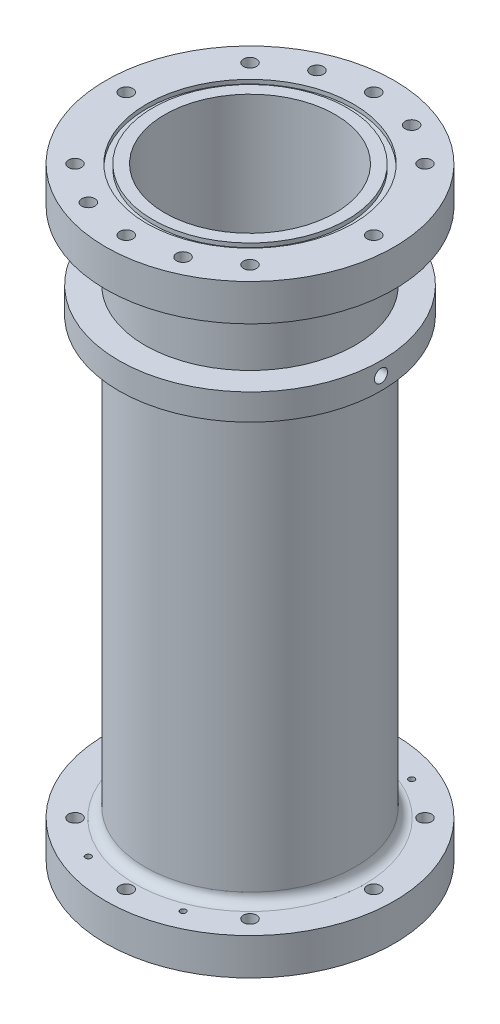
SolidWorks part; units mm, degrees
ref_plane "Front Plane" through (0, 0, 0) normal (0, 0, 1) x (1, 0, 0)
ref_plane "Top Plane" through (0, 0, 0) normal (0, 1, 0) x (1, 0, 0)
ref_plane "Right Plane" through (0, 0, 0) normal (1, 0, 0) x (0, 0, -1)
sketch "Sketch2" plane through (0, 0, 0) normal (0, 1, 0) x (1, 0, 0)
  circle A0 centre (0, 0) radius 41.275
  circle A1 centre (0, 0) radius 50.8
  dimension "D1" = 101.6
  dimension "D2" = 82.55
extrude "Base Cylinder" add sketch "Sketch2" along normal blind 292.1
sketch "Sketch3" plane through (0, 0, 0) normal (0, -1, 0) x (1, 0, 0)
  circle A0 centre (0, 0) radius 41.275
  circle A1 centre (0, 0) radius 69.85
  dimension "D1" = 139.7
extrude "Aft Flange" add sketch "Sketch3" against normal blind 17.78
sketch "Sketch4" plane through (0, 292.1, 0) normal (0, 1, 0) x (1, 0, 0)
  circle A0 centre (0, 0) radius 41.275
  circle A1 centre (0, 0) radius 69.85
extrude "Forward Flange" add sketch "Sketch4" against normal blind 17.78
sketch "Sketch6" plane through (0, 0, 0) normal (0, -1, 0) x (1, 0, 0)
  circle A0 centre (0, 0) radius 50.0761
  circle A1 centre (0, 0) radius 47.0027
  dimension "D1" = 100.1522
  dimension "D2" = 94.0054
extrude "O-Ring Slot 1" cut sketch "Sketch6" against normal blind 1.9812
sketch "Sketch7" plane through (0, 292.1, 0) normal (0, 1, 0) x (1, 0, 0)
  circle A0 centre (0, 0) radius 50.0761
  circle A1 centre (0, 0) radius 47.0027
  dimension "D1" = 100.1522
  dimension "D2" = 94.0054
extrude "O-Ring Slot 2" cut sketch "Sketch7" against normal blind 1.9812
sketch "Sketch8" plane through (0, 0, 0) normal (0, -1, 0) x (1, 0, 0)
  circle A0 centre (-59.9186, 0) radius 3.175
  circle A1 centre (-42.3688, 42.3688) radius 3.175
  circle A2 centre (0, 59.9186) radius 3.175
  circle A3 centre (42.3688, 42.3688) radius 3.175
  circle A4 centre (59.9186, 0) radius 3.175
  circle A5 centre (42.3688, -42.3688) radius 3.175
  circle A6 centre (0, -59.9186) radius 3.175
  circle A7 centre (-42.3688, -42.3688) radius 3.175
  point P36 (0, 0)
  dimension "D2" = 6.35
  dimension "D1" = 59.9186
  dimension "D3" = 8
extrude "Cut-Extrude4" cut sketch "Sketch8" against normal through all both and the other way through all
fillet "Fillet1" radius 4.7625 2 edges at (0, 17.78, -50.8) (0, 274.32, 50.8)
sketch "Sketch9" plane through (0, 292.1, 0) normal (0, 1, 0) x (1, 0, 0)
  line L0 (0, -76.2) -> (0, 76.2) construction
  line L1 (-32.6024, 78.7092) -> (32.6024, -78.7092) construction
  line L2 (-32.0538, -77.3847) -> (32.0538, 77.3847) construction
  circle A0 centre (0, 0) radius 59.9186 construction
  circle A1 centre (-22.9299, 55.3576) radius 3.175
  circle A2 centre (22.9299, -55.3576) radius 3.175
  circle A3 centre (22.9299, 55.3576) radius 3.175
  circle A4 centre (-22.9299, -55.3576) radius 3.175
  point P6 (0, 0)
  point P9 (0, 0)
  point P16 (0, 0)
  dimension "D1" = 119.8372
  dimension "D3" = 6.35
  dimension "D4" = 6.35
  dimension "D5" = 6.35
  dimension "D6" = 6.35
  dimension "D2" = 22.5
  dimension "D7" = 22.5
extrude "Cut-Extrude5" cut sketch "Sketch9" against normal blind 7.62
sketch "Sketch10" plane through (0, 0, 0) normal (0, -1, 0) x (1, 0, 0)
  line L0 (0, -76.2) -> (0, 76.2) construction
  line L1 (-33.7592, 81.5019) -> (33.7592, -81.5019) construction
  line L2 (-33.8465, -81.7128) -> (33.8465, 81.7128) construction
  circle A0 centre (0, 0) radius 59.9186 construction
  circle A1 centre (-22.9299, 55.3576) radius 3.175
  circle A2 centre (22.9299, -55.3576) radius 3.175
  circle A3 centre (22.9299, 55.3576) radius 3.175
  circle A4 centre (-22.9299, -55.3576) radius 3.175
  point P6 (0, 0)
  point P9 (0, 0)
  point P16 (0, 0)
  dimension "D1" = 119.8372
  dimension "D2" = 6.35
  dimension "D3" = 6.35
  dimension "D5" = 6.35
  dimension "D6" = 6.35
  dimension "D4" = 22.5
  dimension "D7" = 22.5
extrude "Cut-Extrude6" cut sketch "Sketch10" against normal blind 7.62
sketch "Sketch11" plane through (0, 284.48, 0) normal (0, 1, 0) x (1, 0, 0)
  circle A0 centre (-22.9299, 55.3576) radius 1.4097
  circle A1 centre (22.9299, 55.3576) radius 1.4097
  circle A2 centre (-22.9299, -55.3576) radius 1.4097
  circle A3 centre (22.9299, -55.3576) radius 1.4097
  dimension "D1" = 2.8194
  dimension "D2" = 2.8194
  dimension "D3" = 2.8194
  dimension "D4" = 2.8194
extrude "Cut-Extrude7" cut sketch "Sketch11" against normal up to next
sketch "Sketch12" plane through (0, 7.62, 0) normal (0, -1, 0) x (1, 0, 0)
  circle A0 centre (-22.9299, 55.3576) radius 1.4097
  circle A1 centre (22.9299, 55.3576) radius 1.4097
  circle A2 centre (-22.9299, -55.3576) radius 1.4097
  circle A3 centre (22.9299, -55.3576) radius 1.4097
  dimension "D1" = 2.8194
  dimension "D2" = 2.8194
  dimension "D3" = 2.8194
  dimension "D4" = 2.8194
extrude "Cut-Extrude8" cut sketch "Sketch12" against normal up to next
ref_plane "Plane1" through (-63.5, 0, 0) normal (1, 0, 0) x (0, 0, -1)
ref_plane "Plane2" through (0, 228.6, 0) normal (0, 1, 0) x (1, 0, 0)
sketch "Sketch14" plane through (0, 228.6, 0) normal (0, 1, 0) x (1, 0, 0)
  circle A0 centre (0, 0) radius 63.5
  circle A1 centre (0, 0) radius 50.8
  dimension "D1" = 101.6
  dimension "D2" = 127
extrude "Boss-Extrude1" add sketch "Sketch14" along normal blind 12.7
sketch "Sketch16" plane through (-63.5, 0, 0) normal (1, 0, 0) x (0, 0, -1)
  line L0 (63.5, 241.3) -> (-63.5, 241.3) construction
  circle A0 centre (0, 234.95) radius 3.175
  dimension "D1" = 6.35
  dimension "D2" = 6.35
extrude "Cut-Extrude10" cut sketch "Sketch16" along normal blind 12.7
ref_plane "Plane3" through (63.5, 0, 0) normal (1, 0, 0) x (0, 0, -1)
sketch "Sketch17" plane through (63.5, 0, 0) normal (1, 0, 0) x (0, 0, -1)
  line L0 (63.5, 241.3) -> (-63.5, 241.3) construction
  circle A0 centre (0, 234.95) radius 3.175
  dimension "D1" = 6.35
  dimension "D2" = 6.35
extrude "Cut-Extrude11" cut sketch "Sketch17" against normal blind 12.7
ref_axis "Axis1" through (50.8, 234.95, 0) along (1, 0, 0)
